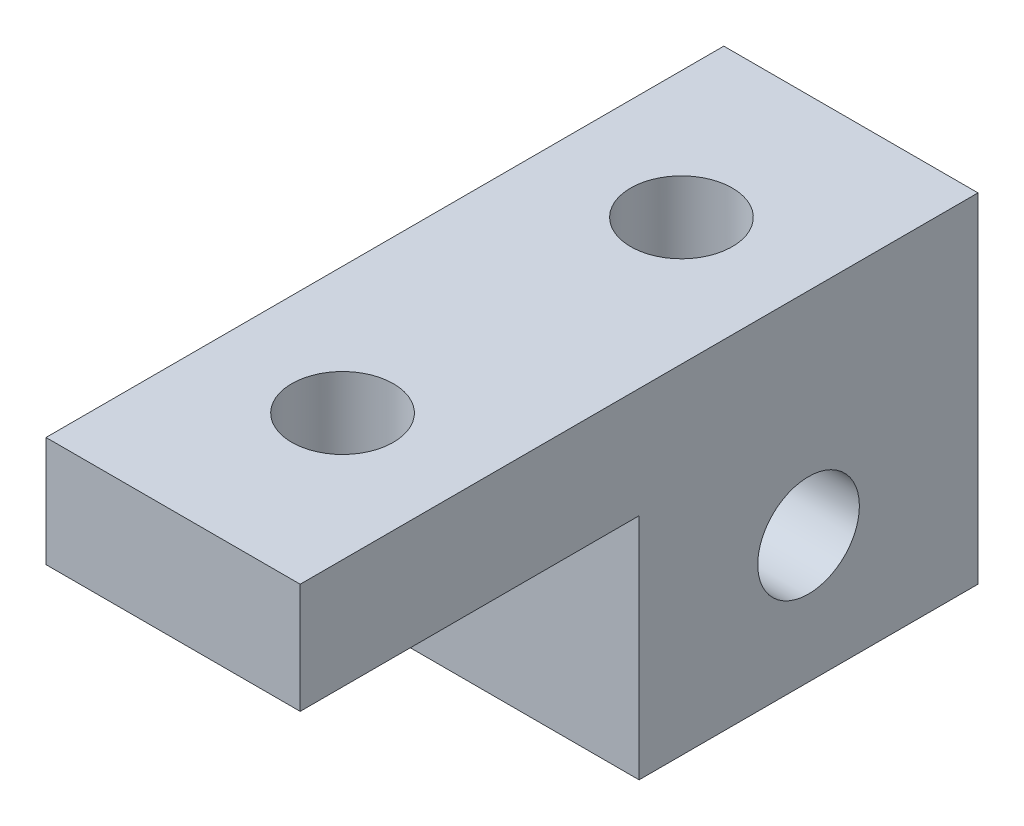
SolidWorks part; units mm, degrees
ref_plane "前视基准面" through (0, 0, 0) normal (0, 0, 1) x (1, 0, 0)
ref_plane "上视基准面" through (0, 0, 0) normal (0, 1, 0) x (1, 0, 0)
ref_plane "右视基准面" through (0, 0, 0) normal (1, 0, 0) x (0, 0, -1)
other "Configuration Table"
sketch "草图1" plane through (0, 0, 0) normal (1, 0, 0) x (0, 0, -1)
  line L1 (-2, 1) -> (2, 1)
  line L2 (-2, 1) -> (-2, -1.5)
  line L3 (-2, -1.5) -> (2, -1.5)
  line L4 (2, 1) -> (2, -1.5)
  line L5 (-2, 1) -> (2, 1)
  line L6 (-2, 1) -> (-2, 2.5)
  line L7 (-2, 2.5) -> (2, 2.5)
  line L8 (2, 1) -> (2, 2.5)
  line L9 (-2, 2.5) -> (-6, 2.5)
  line L10 (-2, 2.5) -> (-2, 1)
  line L11 (-2, 1) -> (-6, 1)
  line L12 (-6, 2.5) -> (-6, 1)
  circle A0 centre (0, 0) radius 0.6
  point P6 (0, -1.5)
  dimension "D1" = 1.2
  dimension "D2" = 1.5
  dimension "D3" = 2
  dimension "D4" = 1.5
  dimension "D5" = 4
  dimension "D6" = 1
extrude "凸台-拉伸1" add sketch "草图1" along normal blind 3 contours L4 L1 L2 L3 A0 | L1 L8 L7 L6 | L9 L12 L11 L6 region at (0, 1.75, 0) region at (0, 0.9528, 0) region at (0, 1.75, 4)
sketch "草图3" plane through (0, 1, 0) normal (0, -1, 0) x (1, 0, 0)
  line L0 (3, 6) -> (0, 6) construction
  line L1 (3, -2) -> (0, -2) construction
  circle A0 centre (1.5, 4) radius 0.6
  circle A1 centre (1.5, 0) radius 0.6
  point P5 (1.5, 6)
  point P9 (0, 0)
  dimension "D2" = 1.2
  dimension "D1" = 2
  dimension "D3" = 2
extrude "切除-拉伸1" cut sketch "草图3" against normal through all both and the other way through all contours A0 | A1
sketch "草图5" plane through (3, 0, 0) normal (1, 0, 0) x (0, 0, -1)
  line L0 (-6, 2.5) -> (-6, 1) construction
  line L1 (-2, 1.2) -> (-6, 1.2)
  line L2 (-2, 1.2) -> (-2, 1)
  line L3 (-2, 1) -> (-6, 1)
  line L4 (-6, 1.2) -> (-6, 1)
  line L5 (-2, 1) -> (-6, 1) construction
  line L6 (-2, 1) -> (-2, -1.5) construction
  dimension "D1" = 0.2
extrude "切除-拉伸2" cut sketch "草图5" against normal through all contours L1 L4 L3 L2
